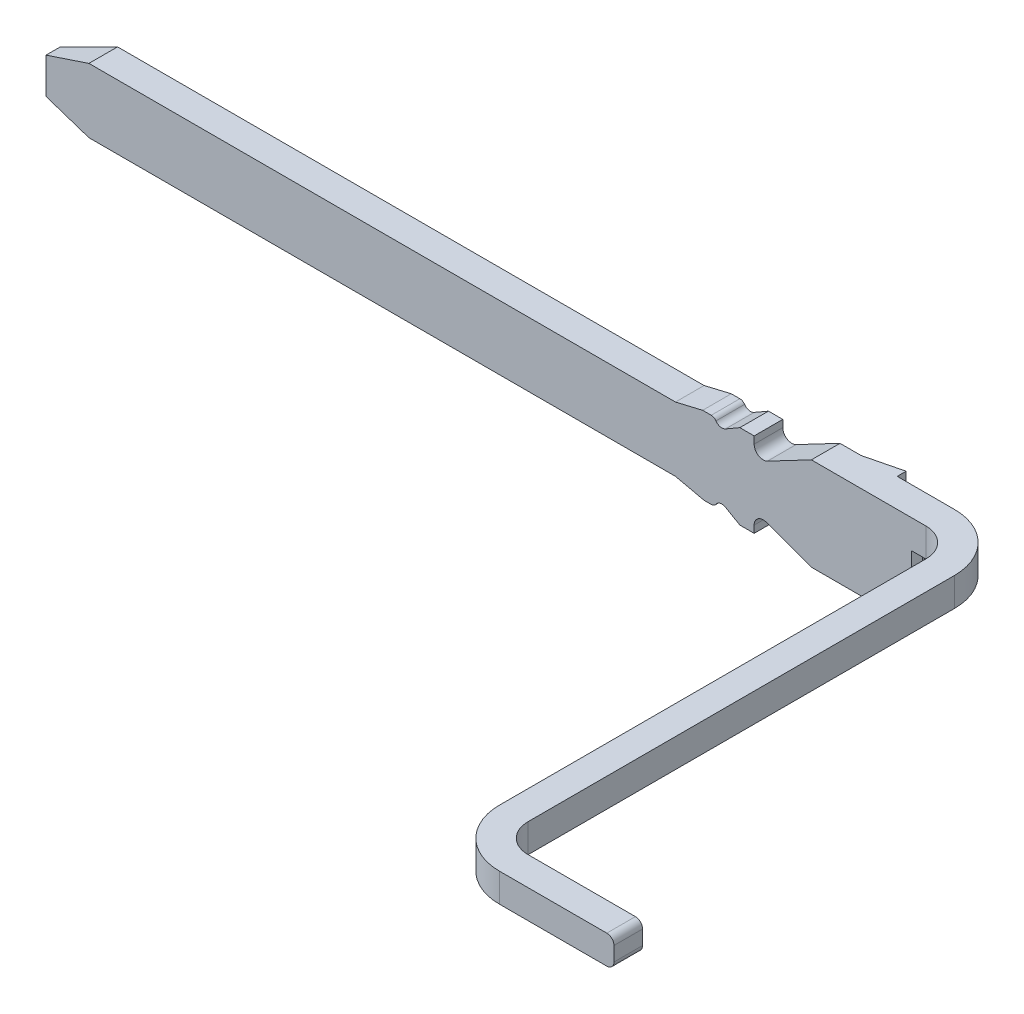
SolidWorks part; units mm, degrees
ref_plane "Plano frontal" through (0, 0, 0) normal (0, 0, 1) x (1, 0, 0)
ref_plane "Plano superior" through (0, 0, 0) normal (0, 1, 0) x (1, 0, 0)
ref_plane "Plano direito" through (0, 0, 0) normal (1, 0, 0) x (0, 0, -1)
sketch "Esboço1" plane through (0, 0, 0) normal (0, 0, 1) x (1, 0, 0)
  line L7 (76.7103, 206.6161) -> (76.7103, 206.4161)
  line L13 (75.9103, 205.9661) -> (76.082, 205.9661)
  line L14 (75.9103, 205.9661) -> (75.5955, 206.0807)
  line L15 (75.5103, 206.0211) -> (75.5103, 205.9711)
  line L16 (75.5103, 205.9711) -> (75.4103, 205.9711)
  line L17 (75.4103, 205.9711) -> (75.3099, 206.0291)
  line L18 (75.2103, 205.9961) -> (75.1603, 205.9961)
  line L19 (75.1603, 205.9961) -> (74.9603, 206.0411)
  line L20 (74.9603, 206.0411) -> (70.8603, 206.0411)
  line L21 (70.8603, 206.0411) -> (70.5603, 206.1411)
  line L22 (70.5603, 206.1411) -> (70.5603, 206.3911)
  line L23 (70.5603, 206.3911) -> (70.8603, 206.4911)
  line L24 (70.8603, 206.4911) -> (74.9603, 206.4911)
  line L25 (74.9603, 206.4911) -> (75.1503, 206.5361)
  line L26 (75.1503, 206.5361) -> (75.2103, 206.5361)
  line L27 (75.3099, 206.5031) -> (75.4103, 206.5611)
  line L28 (75.4103, 206.5611) -> (75.5103, 206.5611)
  line L29 (75.5103, 206.5611) -> (75.5103, 206.5111)
  line L30 (75.6032, 206.4549) -> (75.9103, 206.6161)
  line L35 (76.6103, 206.1161) -> (76.5603, 206.1161)
  line L36 (76.5103, 206.0661) -> (76.5103, 205.9661)
  line L37 (76.5103, 205.9661) -> (76.1103, 205.9661)
  line L38 (76.1103, 206.6161) -> (76.7103, 206.6161)
  line L39 (76.082, 206.6161) -> (75.9103, 206.6161)
  line L40 (76.7103, 206.4161) -> (76.6573, 206.4161)
  line L41 (76.6453, 206.1161) -> (76.6103, 206.1161)
  line L43 (76.1103, 205.9661) -> (76.082, 205.9661)
  line L44 (76.1103, 206.6161) -> (76.082, 206.6161)
  line L45 (76.6573, 206.1161) -> (76.6573, 206.4161)
  line L46 (76.6573, 206.1161) -> (76.6453, 206.1161)
  arc A2 (75.5955, 206.0807) -> (75.5103, 206.0211) centre (75.5738, 206.0211) ccw
  arc A3 (75.3099, 206.0291) -> (75.2435, 206.0137) centre (75.2849, 205.9858) ccw
  arc A4 (75.2103, 205.9961) -> (75.2435, 206.0137) centre (75.2103, 206.0361) ccw
  arc A5 (75.2435, 206.5185) -> (75.2103, 206.5361) centre (75.2103, 206.4961) ccw
  arc A6 (75.2435, 206.5185) -> (75.3099, 206.5031) centre (75.2849, 206.5465) ccw
  arc A7 (75.5103, 206.5111) -> (75.6032, 206.4549) centre (75.5738, 206.5111) ccw
  arc A8 (76.5603, 206.1161) -> (76.5103, 206.0661) centre (76.5603, 206.0661) ccw
extrude "Ressalto-extrusão1" add sketch "Esboço1" along normal blind 0.2
sketch "Esboço2" plane through (0, 206.4161, 0) normal (0, -1, 0) x (1, 0, 0)
  line L3 (76.7103, 0.2) -> (76.7103, 0) construction
  line L4 (76.7103, 0) -> (76.7103, 0.2)
  line L5 (76.9103, 0.4) -> (76.9103, 3.38)
  line L7 (77.1103, 0.4) -> (77.1103, 3.38)
  line L10 (77.3103, 3.58) -> (78.1103, 3.58)
  line L12 (77.3103, 3.78) -> (78.1103, 3.78)
  line L13 (78.1103, 3.58) -> (78.1103, 3.78)
  arc A0 (76.7103, 0) -> (77.1103, 0.4) centre (76.7103, 0.4) ccw
  arc A1 (76.7103, 0.2) -> (76.9103, 0.4) centre (76.7103, 0.4) ccw
  arc A2 (77.3103, 3.58) -> (77.1103, 3.38) centre (77.3103, 3.38) ccw
  arc A3 (76.9103, 3.38) -> (77.3103, 3.78) centre (77.3103, 3.38) cw
  dimension "D5" = 0.2
  dimension "D6" = 0.4
  dimension "D12" = 0.4
  dimension "D13" = 0.2
  dimension "D1" = 0.2
  dimension "D2" = 0.4
  dimension "D3" = 0.4
  dimension "D4" = 0.2
  dimension "D7" = 2.98
  dimension "D10" = 0.2
  dimension "D11" = 0.8
extrude "Ressalto-extrusão2" add sketch "Esboço2" against normal blind 0.2
sketch "Esboço3" plane through (0, 206.4911, 0) normal (0, 1, 0) x (1, 0, 0)
  line L0 (70.8603, 0) -> (70.5603, -0.1)
  line L1 (70.5603, -0.2) -> (70.5603, 0) construction
  line L2 (70.5603, -0.1) -> (70.4759, -0.1)
  line L3 (70.4759, -0.1) -> (70.4759, 0.0985)
  line L4 (70.4759, 0.0985) -> (70.8603, 0.0985)
  line L5 (70.8603, 0.0985) -> (70.8603, 0)
  dimension "D1" = 0.1
extrude "Corte-extrusão1" cut sketch "Esboço3" against normal blind 1
fillet "Filete1" radius 0.05 2 edges at (78.1103, 206.4161, 3.68) (78.1103, 206.6161, 3.68)
sketch "Esboço4" plane through (0, 206.6161, 0) normal (0, 1, 0) x (1, 0, 0)
  line L0 (76.0576, 0) -> (76.3103, 0)
  line L1 (76.7103, 0) -> (75.9103, 0) construction
  line L2 (76.3103, 0) -> (76.3103, 0.0624)
  line L3 (76.3103, 0.0624) -> (76.0576, 0)
  dimension "D1" = 0.2527
  dimension "D2" = 0.0624
  dimension "D3" = 5.4973
extrude "Ressalto-extrusão3" add sketch "Esboço4" against normal blind 0.145
pattern_linear "Padrão linear1" count 2 spacing 0.505 along (0, -1, 0) of "Ressalto-extrusão3"
sketch "Esboço5" plane through (0, 206.1161, 0) normal (0, -1, 0) x (1, 0, 0)
  line L0 (76.6573, 0.16) -> (76.6453, 0.16)
  line L1 (76.6573, 0.2) -> (76.6573, 0) construction
  line L2 (76.6453, 0.16) -> (76.6088, 0.2)
  line L3 (76.5603, 0.2) -> (76.6573, 0.2) construction
  line L4 (76.6088, 0.2) -> (76.6088, 0.2324)
  line L5 (76.6088, 0.2324) -> (76.6797, 0.2324)
  line L6 (76.6797, 0.2324) -> (76.6797, 0.16)
  line L7 (76.6797, 0.16) -> (76.6573, 0.16)
  line L8 (76.6088, 0) -> (76.6453, 0.04)
  line L9 (76.5603, 0) -> (76.6573, 0) construction
  line L10 (76.6453, 0.04) -> (76.6797, 0.04)
  line L11 (76.6797, 0.04) -> (76.6797, -0.0141)
  line L12 (76.6797, -0.0141) -> (76.6088, -0.0141)
  line L13 (76.6088, 0) -> (76.6088, -0.0141)
  dimension "D1" = 0.012
  dimension "D2" = 0.04
  dimension "D3" = 0.04
extrude "Corte-extrusão2" cut sketch "Esboço5" against normal up to surface (0.3 mm away) up to face at (77.1265, 206.4161, 1.89)
